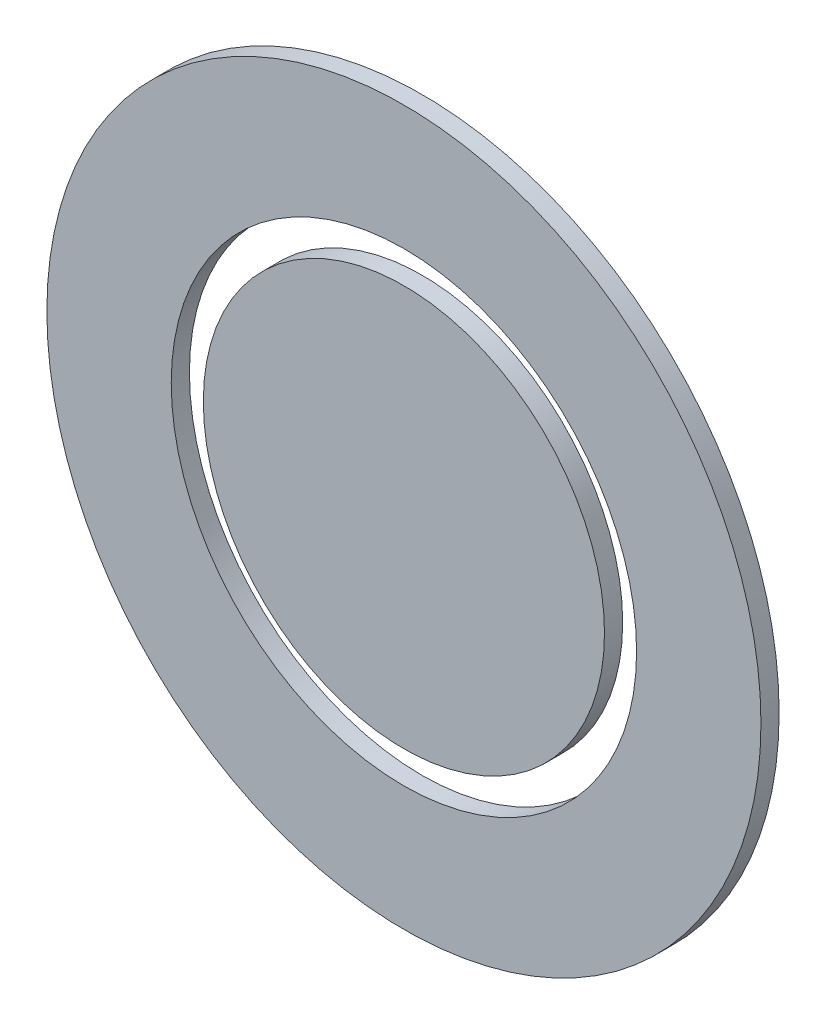
SolidWorks part; units mm, degrees
material "Barium"
ref_plane "Front" through (0, 0, 0) normal (0, 0, 1) x (1, 0, 0)
ref_plane "Top" through (0, 0, 0) normal (0, 1, 0) x (1, 0, 0)
ref_plane "Right" through (0, 0, 0) normal (1, 0, 0) x (0, 0, -1)
sketch "Sketch1" plane through (0, 0, 0) normal (0, 0, 1) x (1, 0, 0)
  circle A0 centre (0, 0) radius 133.5
  circle A1 centre (0, 0) radius 87
  circle A2 centre (0, 0) radius 75
extrude "Boss-Extrude1" add sketch "Sketch1" along normal blind 6.8 contours A2
extrude "Boss-Extrude2" add sketch "Sketch1<4>" along normal blind 6.8 separate body contours A0 | A1
sketch "Sketch1<4>" plane through (0, 0, 0) normal (0, 0, 1) x (1, 0, 0) same geometry as "Sketch1"
